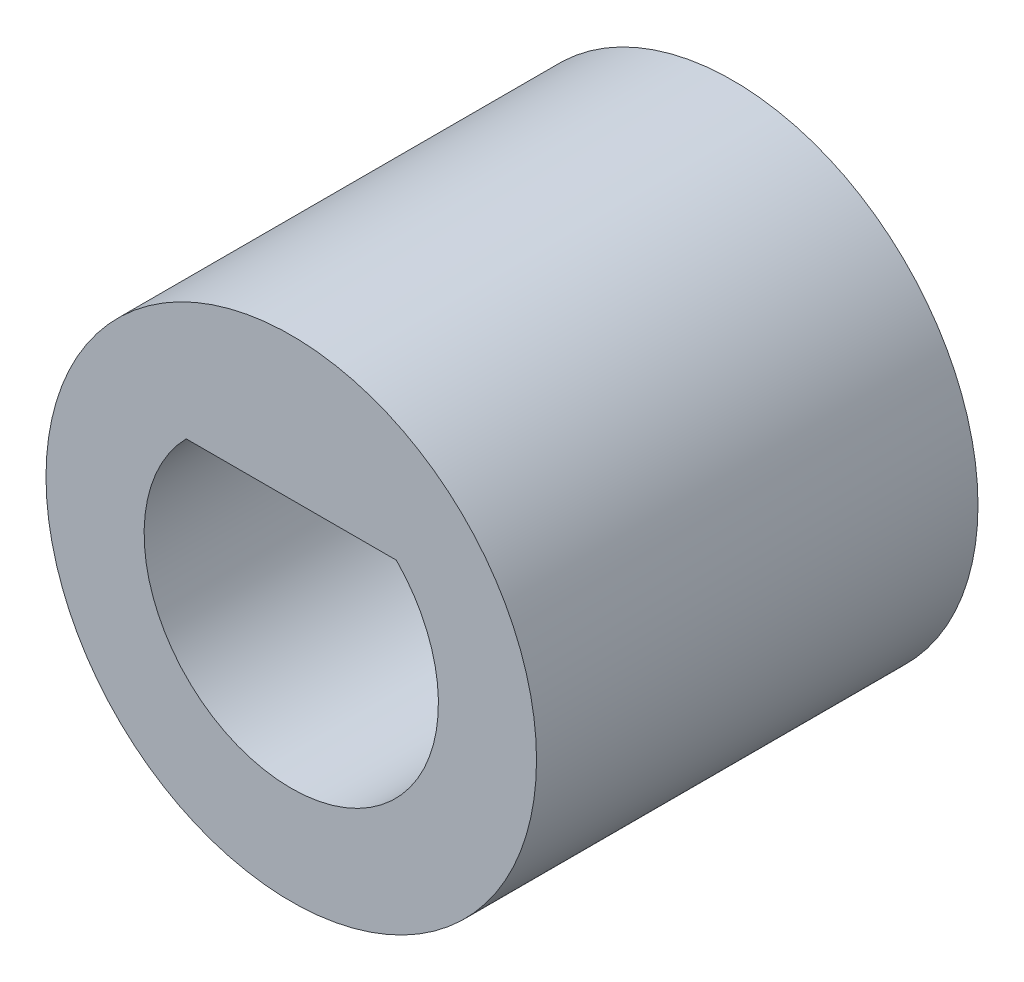
SolidWorks part; units mm, degrees
ref_plane "Plan de face" through (0, 0, 0) normal (0, 0, 1) x (1, 0, 0)
ref_plane "Plan de dessus" through (0, 0, 0) normal (0, 1, 0) x (1, 0, 0)
ref_plane "Plan de droite" through (0, 0, 0) normal (1, 0, 0) x (0, 0, -1)
sketch "Esquisse1" plane through (0, 0, 0) normal (0, 0, 1) x (1, 0, 0)
  line L0 (-2.1424, 2.1) -> (2.1424, 2.1)
  line L1 (-0.9885, -3) -> (1.037, -3) construction
  circle A0 centre (0, 0) radius 5
  arc A1 (-2.1424, 2.1) -> (2.1424, 2.1) centre (0, 0) ccw
  dimension "D1" = 10
  dimension "D2" = 6
  dimension "D3" = 5.1
extrude "Boss.-Extru.1" add sketch "Esquisse1" along normal blind 9
